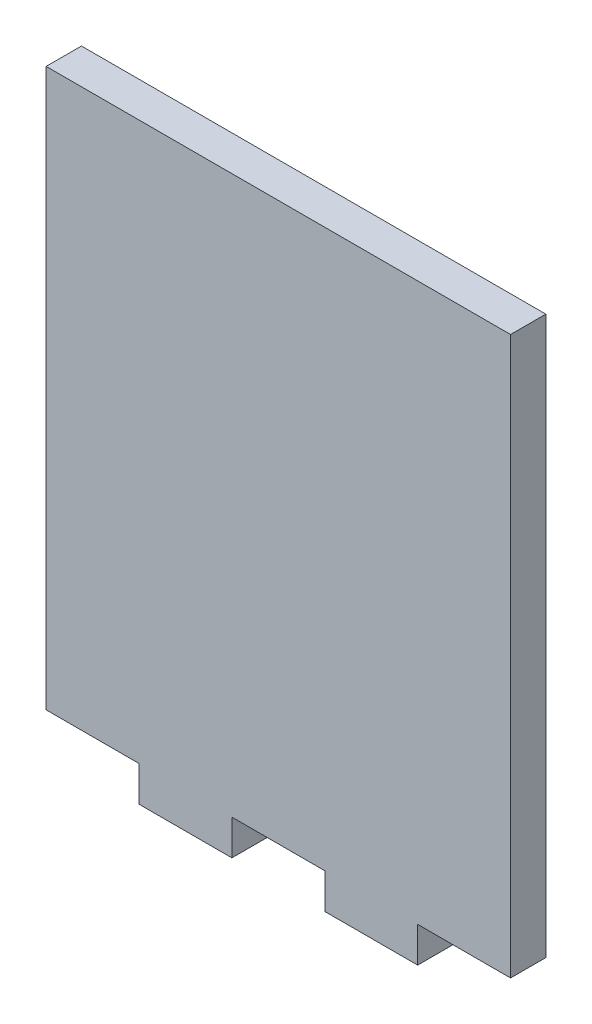
SolidWorks part; units mm, degrees
ref_plane "Front Plane" through (0, 0, 0) normal (0, 0, 1) x (1, 0, 0)
ref_plane "Top Plane" through (0, 0, 0) normal (0, 1, 0) x (1, 0, 0)
ref_plane "Right Plane" through (0, 0, 0) normal (1, 0, 0) x (0, 0, -1)
sketch "Sketch1" plane through (0, 0, 0) normal (0, 0, 1) x (1, 0, 0)
  line L1 (0, 0) -> (63.5, 0)
  line L2 (0, 0) -> (0, 81.026)
  line L3 (0, 81.026) -> (63.5, 81.026)
  line L4 (63.5, 0) -> (63.5, 81.026)
  dimension "D1" = 81.026
  dimension "D2" = 63.5
extrude "Boss-Extrude1" add sketch "Sketch1" along normal blind 4.826
sketch "Sketch2" plane through (0, 0, 4.826) normal (0, 0, 1) x (1, 0, 0)
  line L0 (0, 0) -> (63.5, 0) construction
  line L1 (0, 0) -> (12.7, 0)
  line L2 (0, 0) -> (0, 4.826)
  line L3 (0, 4.826) -> (12.7, 4.826)
  line L4 (12.7, 0) -> (12.7, 4.826)
  line L5 (25.4, 0) -> (38.1, 0)
  line L6 (25.4, 0) -> (25.4, 4.826)
  line L7 (25.4, 4.826) -> (38.1, 4.826)
  line L8 (38.1, 0) -> (38.1, 4.826)
  line L9 (12.7, 4.826) -> (25.4, 4.826) construction
  line L10 (63.5, 0) -> (50.8, 0)
  line L11 (63.5, 0) -> (63.5, 4.826)
  line L12 (63.5, 4.826) -> (50.8, 4.826)
  line L13 (50.8, 0) -> (50.8, 4.826)
  line L14 (38.1, 4.826) -> (50.8, 4.826) construction
  dimension "D1" = 4.826
extrude "Cut-Extrude1" cut sketch "Sketch2" against normal through all
equation "\"MDF\"= 0.19in"
equation "\"PVCID\" = 2.067in"
equation "\"PVCOD\" = 2.375in"
equation "\"GenDiameter\"= 60mm"
equation "\"GenCutDiameter\" = 1.8in"
equation "\"GenCutDistance\" = 1"
equation "\"TowerHeight\" = 6in"
equation "\"TowerFrontBase\" = 3in"
equation "\"FunnelHeight\" = 1in"
equation "\"FunnelAngle\" = 20"
equation "\"TowerSideBase\" = 3in"
equation "\"TowerPanelLength\" = 2in"
equation "\"TowerPanelLeeway\" = 0.5in"
equation "\"BaseLength\" = 9in"
equation "\"BaseWidth\" = 10in"
equation "\"WheelHoleLength\" = 3.25in"
equation "\"WheelHoleWidth\" = 26mm"
equation "\"WheelHoleFromBack\" = 1.5in"
equation "\"DropLength\" = 1in"
equation "\"DropWidth\" = 8.5in"
equation "\"BumperWidth\" = 1in"
equation "\"SmallHexDiameter\" = 0.185in"
equation "\"SmallHexHeight\" = 0.701in"
equation "\"ScrewSize\" = 0.106in"
equation "\"BigHexDiameter\" = 0.251in"
equation "\"BigHexHeight\" = 0.374in"
equation "\"PCBThickness\" = 0.066in"
equation "\"ConnectorHeight\" = 0.517in"
equation "\"BoardHeight\" = 0.583in"
equation "\"UnoStackHeight\" = 1.351in"
equation "\"UnoStackWidth\" = 3.053in"
equation "\"UnoStackLength\" = 3.152in"
equation "\"HBridgeWidth\" = 1.797in"
equation "\"HBridgeLength\" = 2.236in"
equation "\"DSWidth\" = 1.820in"
equation "\"DSLength\" = 1.833in"
equation "\"StepperWidth\" = 1.799in"
equation "\"StepperLength\" = 2.248in"
equation "\"ULNWidth\" = 1.304in"
equation "\"ULNLength\" = 1.545in"
equation "\"VSwitchHeight\" = 0.392in"
equation "\"VSwitchWidth\" = 0.637in"
equation "\"VSwitchLength\" = 1.097in"
equation "\"SkateWheelDiameter\" = 80mm"
equation "\"SkateWheelThickness\" = 24mm"
equation "\"BaseDistance\" = 3in"
equation "\"DummyVar\" = 2in"
equation "\"D1@Sketch1\"=\"MDF\"+3in"
equation "\"D1@Boss-Extrude1\"=\"MDF\""
equation "\"D1@Sketch2\"=\"MDF\""
